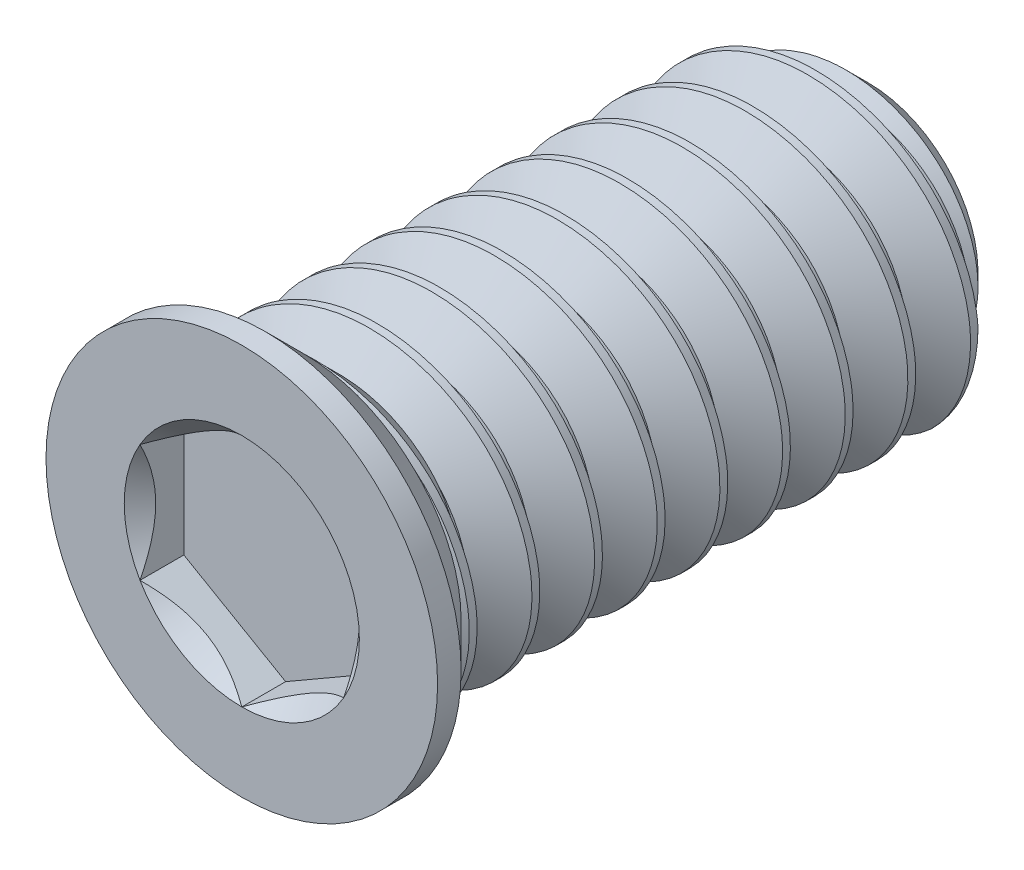
SolidWorks part; units mm, degrees
ref_plane "Front" through (0, 0, 0) normal (0, 0, 1) x (1, 0, 0)
ref_plane "Top" through (0, 0, 0) normal (0, 1, 0) x (1, 0, 0)
ref_plane "Right" through (0, 0, 0) normal (1, 0, 0) x (0, 0, -1)
sketch "Sketch1" plane through (0, 0, 0) normal (1, 0, 0) x (0, 0, -1)
  line L0 (0, 1.25) -> (0.15, 1.25) construction
  line L1 (0.15, 1.25) -> (0.4, 1) construction
  line L2 (0, 1) -> (4, 1)
  line L3 (4, 1) -> (4, 0)
  line L4 (4, 0) -> (0, 0)
  line L5 (0, 0) -> (0, 1.25) construction
  line L6 (0, 1.25) -> (0, -1.25) construction
  line L7 (4, 1) -> (4, -1) construction
  line L8 (0, -1.25) -> (0.15, -1.25) construction
  line L9 (0.15, -1.25) -> (0.4, -1) construction
  line L11 (0, 1) -> (0, 0)
  line L12 (0.4, 1) -> (0.4, 0) construction
revolve "Revolve1" add sketch "Sketch1" angle 360 mid plane about L4
sketch "Sketch3" plane through (0, 0, -4) normal (0, 0, -1) x (-1, 0, 0)
  circle A0 centre (0, 0) radius 1
curve "Helix/Spiral1" pitch 0.4 height 4 radius 1 centre (0, 0, -4) axis (0, 0, 1) start towards (0, 1, 0)
sketch "Sketch2" plane through (0, 0, 0) normal (1, 0, 0) x (0, 0, -1)
  line L0 (4, 1) -> (4.35, 1)
  line L1 (4.35, 1) -> (4.2, 0.7402)
  line L2 (4.2, 0.7402) -> (4.15, 0.7402)
  line L3 (4.15, 0.7402) -> (4, 1)
  line L4 (4.075, 0.8701) -> (4.275, 0.8701) construction
  dimension "D1" = 60
  dimension "D2" = 0.05
  dimension "D3" = 0.2
chamfer "Chamfer1" distance 0.3 angle 45 1 edges at (0, 1, -4)
sweep "Cut-Sweep1" cut profiles "Sketch2" path "Helix/Spiral1" align with end faces yes
sketch "Sketch7" plane through (0, 0, 0) normal (1, 0, 0) x (0, 0, -1)
  line L0 (0, 1.25) -> (0.15, 1.25) construction
  line L1 (0.15, 1.25) -> (0.4, 1) construction
  line L2 (0, 1.25) -> (0.15, 1.25)
  line L3 (0.15, 1.25) -> (0.4, 1)
  line L4 (0.4, 1) -> (0.4, 0) construction
  line L5 (0.4, 1) -> (0.4, 0)
  line L7 (0, 0) -> (0, 1.25) construction
  line L8 (0, 0) -> (0, 1.25)
  line L9 (0, 0) -> (0.4, 0)
  line L10 (55, 0) -> (-55, 0) construction
revolve "Revolve2" add sketch "Sketch7" angle 360 mid plane about L9
ref_plane "Plane1" through (0, 0, -0.4) normal (0, 0, 1) x (1, 0, 0)
sketch "Sketch8" plane through (0, 0, -0.4) normal (0, 0, 1) x (1, 0, 0)
  circle A0 centre (0, 0) radius 1
extrude "Boss-Extrude1" add sketch "Sketch8" against normal through all draft 45
sketch "Sketch5" plane through (0, 0, 0) normal (0, 0, 1) x (1, 0, 0)
  line L1 (0.65, -0.3753) -> (0.65, 0.3753)
  line L2 (0.65, 0.3753) -> (0, 0.7506)
  line L3 (0, 0.7506) -> (-0.65, 0.3753)
  line L4 (-0.65, 0.3753) -> (-0.65, -0.3753)
  line L5 (-0.65, -0.3753) -> (0, -0.7506)
  line L6 (0, -0.7506) -> (0.65, -0.3753)
  circle A0 centre (0, 0) radius 0.65 construction
  dimension "Hex" = 1.3
extrude "Cut-Extrude2" cut sketch "Sketch5" against normal blind 0.28
sketch "Sketch6" plane through (0, 0, 0) normal (0, 0, 1) x (1, 0, 0)
  circle A0 centre (0, 0) radius 0.7506
extrude "Cut-Extrude3" cut sketch "Sketch6" against normal blind 0.28 draft 45
sketch "Sketch9" [suppressed] plane through (0, 0, -5.5) normal (0, 0, 1) x (1, 0, 0)
  circle A1 centre (0, 0) radius 5
  circle A2 centre (0, 0) radius 5
  point P0 (0, 5)
  dimension "D1" = 0
extrude "Boss-Extrude2" [suppressed] add sketch "Sketch9" against normal offset from surface (18.5 mm away) 26 up to face at (0, 0.7, -4)
fillet "Fillet1" [suppressed] radius 0.2
sketch "Sketch10" plane through (0, 0, 0) normal (1, 0, 0) x (0, 0, -1)
  line L0 (4, 1) -> (4, -1) construction
  point P0 (3.4, -1)
  dimension "D1" = 0.6
equation "\"D3@Helix/Spiral1\" = \"Lg@Sketch1\""
equation "\"D2@Sketch2\" = \"D4@Helix/Spiral1\" * .125"
equation "\"D3@Sketch2\" = \"D4@Helix/Spiral1\" * .5"
equation "\"D1@Chamfer1\" = \"D4@Helix/Spiral1\" * .75"
equation "\"D1@Cut-Extrude2\" = \"Head Ht@Sketch1\" * .7"
equation "\"D1@Sketch10\" = \"D4@Helix/Spiral1\" * 1.5"
equation "\"D1@Cut-Extrude3\" = \"D1@Cut-Extrude2\""
equation "\"D1@Fillet1\" = \"Dia@Sketch1\" * .1"
